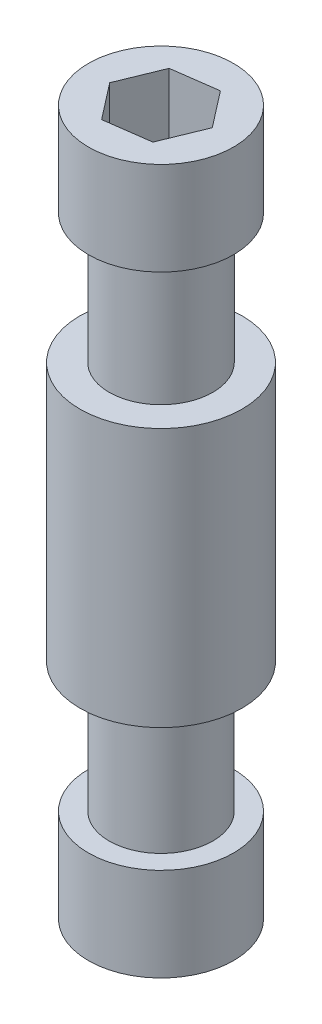
SolidWorks part; units mm, degrees
ref_plane "Front Plane" through (0, 0, 0) normal (0, 0, 1) x (1, 0, 0)
ref_plane "Top Plane" through (0, 0, 0) normal (0, 1, 0) x (1, 0, 0)
ref_plane "Right Plane" through (0, 0, 0) normal (1, 0, 0) x (0, 0, -1)
sketch "Sketch1" plane through (0, 0, 0) normal (0, 1, 0) x (1, 0, 0)
  circle A0 centre (0, 0) radius 3.9688
  dimension "D1" = 7.9375
extrude "Boss-Extrude1" add sketch "Sketch1" along normal blind 12.7
sketch "Sketch2" plane through (0, 12.7, 0) normal (0, 1, 0) x (1, 0, 0)
  circle A0 centre (0, 0) radius 2.54
extrude "Boss-Extrude2" add sketch "Sketch2" along normal blind 6.35
sketch "Sketch3" plane through (0, 19.05, 0) normal (0, 1, 0) x (1, 0, 0)
  circle A0 centre (0, 0) radius 3.556
extrude "Boss-Extrude3" add sketch "Sketch3" along normal blind 4.572
sketch "Sketch4" plane through (0, 23.622, 0) normal (0, 1, 0) x (1, 0, 0)
  line L1 (2.2126, 0.302) -> (0.8447, 2.0671)
  line L2 (0.8447, 2.0671) -> (-1.3678, 1.7651)
  line L3 (-1.3678, 1.7651) -> (-2.2126, -0.302)
  line L4 (-2.2126, -0.302) -> (-0.8447, -2.0671)
  line L5 (-0.8447, -2.0671) -> (1.3678, -1.7651)
  line L6 (1.3678, -1.7651) -> (2.2126, 0.302)
  circle A0 centre (0, 0) radius 1.9339 construction
extrude "Cut-Extrude1" cut sketch "Sketch4" against normal blind 3.556
ref_plane "Plane1" through (0, 6.35, 0) normal (0, 1, 0) x (1, 0, 0)
mirror "Mirror1" about plane through (0, 6.35, 0) normal (0, 1, 0) of "Cut-Extrude1", "Boss-Extrude3", "Boss-Extrude2"
